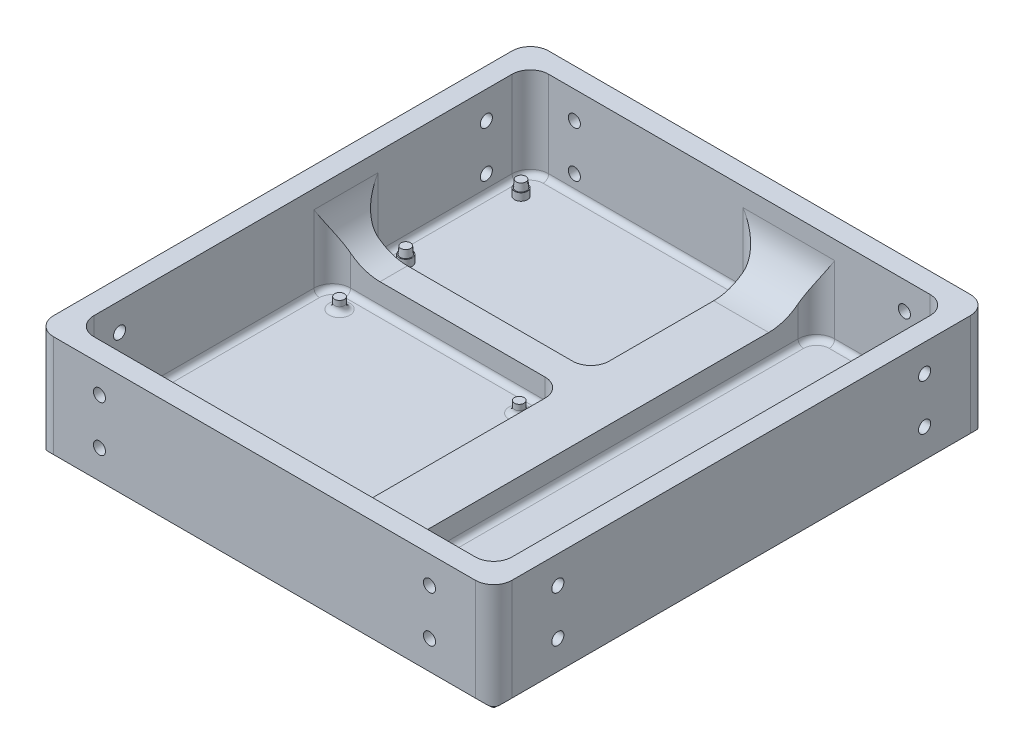
SolidWorks part; units mm, degrees
ref_plane "Front Plane" through (0, 0, 0) normal (0, 0, 1) x (1, 0, 0)
ref_plane "Top Plane" through (0, 0, 0) normal (0, 1, 0) x (1, 0, 0)
ref_plane "Right Plane" through (0, 0, 0) normal (1, 0, 0) x (0, 0, -1)
sketch "Sketch1" plane through (0, 0, 0) normal (0, 1, 0) x (1, 0, 0)
  line L1 (-83.6568, 40.258) -> (46.3432, 40.258)
  line L2 (-83.6568, 40.258) -> (-83.6568, -99.742)
  line L3 (-83.6568, -99.742) -> (46.3432, -99.742)
  line L4 (46.3432, 40.258) -> (46.3432, -99.742)
  dimension "D1" = 140
  dimension "D2" = 130
extrude "Boss-Extrude2" add sketch "Sketch1" along normal blind 10
sketch "Sketch3" plane through (0, 10, 0) normal (0, 1, 0) x (1, 0, 0)
  line L0 (-83.6568, -99.742) -> (46.3432, -99.742) construction
  line L1 (-83.6568, 40.258) -> (-83.6568, -99.742) construction
  circle A0 centre (-68.6568, -26.742) radius 1.3
  circle A1 centre (-19.6568, -26.742) radius 1.3
  circle A2 centre (-68.6568, -84.742) radius 1.3
  circle A3 centre (-19.6568, -84.742) radius 1.3
  dimension "D1" = 49
  dimension "D2" = 58
  dimension "D3" = 49
  dimension "D6" = 2.6
  dimension "D7" = 2.6
  dimension "D8" = 2.6
  dimension "D9" = 2.6
  dimension "D4" = 15
  dimension "D5" = 15
extrude "Boss-Extrude4" add sketch "Sketch3" along normal blind 2
sketch "Sketch4" plane through (0, 12, 0) normal (0, 1, 0) x (1, 0, 0)
  circle A0 centre (-68.6568, -26.742) radius 1.15
  circle A1 centre (-68.6568, -84.742) radius 1.15
  circle A2 centre (-19.6568, -84.742) radius 1.15
  circle A3 centre (-19.6568, -26.742) radius 1.15
  dimension "D1" = 2.3
  dimension "D2" = 2.3
  dimension "D3" = 2.3
  dimension "D4" = 2.3
extrude "Boss-Extrude5" add sketch "Sketch4" along normal blind 3 draft 5 draft outward yes
chamfer "Chamfer1" distance 1.5 angle 45 4 edges at (-19.6568, 15, 86.1545) (-68.6568, 15, 28.1545) (-19.6568, 15, 28.1545) (-68.6568, 15, 86.1545)
sketch "Sketch5" plane through (0, 10, 0) normal (0, 1, 0) x (1, 0, 0)
  line L0 (46.3432, 40.258) -> (-83.6568, 40.258) construction
  line L1 (-83.6568, -99.742) -> (-73.6568, -99.742)
  line L2 (-83.6568, -99.742) -> (-83.6568, 40.258)
  line L3 (-83.6568, 40.258) -> (-73.6568, 40.258)
  line L4 (-73.6568, -89.742) -> (-73.6568, 30.258)
  line L5 (46.3432, -99.742) -> (46.3432, 40.258) construction
  line L6 (46.3432, 40.258) -> (-83.6568, 40.258)
  line L7 (46.3432, 40.258) -> (46.3432, 30.258)
  line L8 (36.3432, 30.258) -> (-73.6568, 30.258)
  line L9 (-83.6568, 40.258) -> (-83.6568, 30.258)
  line L10 (-83.6568, -99.742) -> (46.3432, -99.742)
  line L11 (-83.6568, -99.742) -> (-83.6568, -89.742)
  line L12 (-73.6568, -89.742) -> (36.3432, -89.742)
  line L13 (46.3432, -99.742) -> (46.3432, -89.742)
  line L15 (46.3432, -99.742) -> (36.3432, -99.742)
  line L16 (46.3432, -99.742) -> (46.3432, 40.258)
  line L17 (46.3432, 40.258) -> (36.3432, 40.258)
  line L18 (36.3432, -89.742) -> (36.3432, 30.258)
  line M3 (-83.6568, 40.258) -> (-83.6568, -99.742)
  line M4 (-83.6568, -99.742) -> (46.3432, -99.742)
  line M5 (46.3432, -99.742) -> (46.3432, 40.258)
  line M6 (46.3432, 40.258) -> (-83.6568, 40.258)
  dimension "D1" = 10
  dimension "D2" = 10
  dimension "D3" = 10
  dimension "D4" = 10
extrude "Boss-Extrude6" add sketch "Sketch5" along normal blind 20 contours L6 L2 L10 L18 L12 L4 L8 M6 M3 M4 M5
sketch "Sketch7" plane through (0, 30, 0) normal (0, 1, 0) x (1, 0, 0)
  line L0 (46.3432, 40.258) -> (-83.6568, 40.258) construction
  line L1 (-75.6568, 32.258) -> (38.3432, 32.258)
  line L2 (-75.6568, 32.258) -> (-75.6568, -91.742)
  line L3 (-75.6568, -91.742) -> (38.3432, -91.742)
  line L4 (38.3432, 32.258) -> (38.3432, -91.742)
  line L5 (-83.6568, -99.742) -> (46.3432, -99.742) construction
  line L6 (-83.6568, 40.258) -> (-83.6568, -99.742) construction
  line L7 (46.3432, -99.742) -> (46.3432, 40.258) construction
  line L9 (-73.6568, 30.258) -> (36.3432, 30.258)
  line L10 (-73.6568, 30.258) -> (-73.6568, -89.742)
  line L11 (-73.6568, -89.742) -> (36.3432, -89.742)
  line L12 (36.3432, 30.258) -> (36.3432, -89.742)
  dimension "D1" = 8
  dimension "D2" = 8
  dimension "D3" = 8
  dimension "D4" = 8
extrude "Cut-Extrude2" cut sketch "Sketch7" against normal up to surface (20 mm away) up to face at (-18.6568, 10, 29.742)
sketch "Sketch9" plane through (0, 10, 0) normal (0, 1, 0) x (1, 0, 0)
  line L0 (38.3432, -91.742) -> (-75.6568, -91.742) construction
  line L1 (-12.6568, -91.742) -> (2.3432, -91.742)
  line L2 (-12.6568, -91.742) -> (-12.6568, 32.258)
  line L3 (-12.6568, 32.258) -> (2.3432, 32.258)
  line L4 (2.3432, -91.742) -> (2.3432, 32.258)
  line L5 (38.3432, -91.742) -> (38.3432, 32.258) construction
  line L6 (-75.6568, 32.258) -> (38.3432, 32.258) construction
  dimension "D1" = 15
  dimension "D2" = 36
  dimension "D3" = 0
extrude "Boss-Extrude8" add sketch "Sketch9" along normal blind 5
sketch "Sketch10" plane through (0, 10, 0) normal (0, 1, 0) x (1, 0, 0)
  line L0 (-75.6568, -91.742) -> (-75.6568, 32.258) construction
  line L1 (-75.6568, -21.742) -> (-12.6568, -21.742)
  line L2 (-75.6568, -21.742) -> (-75.6568, -14.242)
  line L3 (-75.6568, -14.242) -> (-12.6568, -14.242)
  line L4 (-12.6568, -21.742) -> (-12.6568, -14.242)
  line L5 (-12.6568, 32.258) -> (-12.6568, -91.742) construction
  circle A0 centre (-68.6568, -26.742) radius 1.2817 construction
  dimension "D1" = 7.5
  dimension "D2" = 5
extrude "Boss-Extrude9" add sketch "Sketch10" along normal blind 5
sketch "Sketch12" plane through (0, 10, 0) normal (0, 1, 0) x (1, 0, 0)
  line L1 (-75.6568, 32.258) -> (-12.6568, 32.258)
  line L2 (-75.6568, 32.258) -> (-75.6568, -14.242)
  line L3 (-75.6568, -14.242) -> (-12.6568, -14.242)
  line L4 (-12.6568, 32.258) -> (-12.6568, -14.242)
  line L5 (2.3432, 32.258) -> (38.3432, 32.258)
  line L6 (2.3432, 32.258) -> (2.3432, -91.742)
  line L7 (2.3432, -91.742) -> (38.3432, -91.742)
  line L8 (38.3432, 32.258) -> (38.3432, -91.742)
  line L9 (-12.6568, -91.742) -> (-75.6568, -91.742)
  line L10 (-12.6568, -91.742) -> (-12.6568, -21.742)
  line L11 (-12.6568, -21.742) -> (-75.6568, -21.742)
  line L12 (-75.6568, -91.742) -> (-75.6568, -21.742)
  circle A0 centre (-68.6846, -26.742) radius 1.3279
  circle A1 centre (-68.6568, -26.742) radius 0.0279 construction
  circle A2 centre (-19.6568, -26.7699) radius 1.3279
  circle A3 centre (-19.6568, -26.742) radius 0.0279 construction
  circle A4 centre (-19.6289, -84.742) radius 1.2539
  circle A5 centre (-19.6568, -84.742) radius 0.0279 construction
  circle A6 centre (-68.6568, -84.7141) radius 1.2539
  circle A7 centre (-68.6568, -84.742) radius 0.0279 construction
extrude "Cut-Extrude6" cut sketch "Sketch12" against normal blind 5
sketch "Sketch14" plane through (0, 15, 0) normal (0, 1, 0) x (1, 0, 0)
  line L1 (-75.6568, -21.742) -> (-15.6932, -21.742)
  line L2 (-75.6568, -21.742) -> (-75.6568, -90.2178)
  line L3 (-75.6568, -90.2178) -> (-15.6932, -90.2178)
  line L4 (-15.6932, -21.742) -> (-15.6932, -90.2178)
extrude "Cut-Extrude9" cut sketch "Sketch14" against normal blind 7
sketch "Sketch16" plane through (0, 15, 0) normal (0, 1, 0) x (1, 0, 0)
  line L1 (-75.6568, 32.258) -> (38.3432, 32.258)
  line L2 (-75.6568, 32.258) -> (-75.6568, -91.742)
  line L3 (-75.6568, -91.742) -> (38.3432, -91.742)
  line L4 (38.3432, 32.258) -> (38.3432, -91.742)
extrude "Cut-Extrude10" cut sketch "Sketch16" against normal blind 3
fillet "Fillet12" radius 13 3 edges at (-5.1568, 12, 91.742) (-5.1568, 12, -32.258) (-75.6568, 12, 17.992)
fillet "Fillet13" radius 5 12 edges at (2.3432, 15, 91.742) (-75.6568, 15, 21.742) (-12.6568, 8.5, 21.742) (-75.6568, 17.5, 91.742) (38.3432, 17.5, -32.258) (-12.6568, 15, 91.742) (38.3432, 17.5, 91.742) (2.3432, 15, -32.258) (-75.6568, 15, 14.242) (-12.6568, 8.5, 14.242) (-12.6568, 15, -32.258) (-75.6568, 17.5, -32.258)
fillet "Fillet14" radius 5 4 edges at (46.3432, 15, 99.742) (46.3432, 15, -40.258) (-83.6568, 15, -40.258) (-83.6568, 15, 99.742)
fillet "Fillet15" radius 1.5 28 edges at (3.8077, 5, -30.7935) (20.3432, 5, -32.258) (36.8788, 5, -30.7935) (38.3432, 5, 29.742) (36.8788, 5, 90.2775) (20.3432, 5, 91.742) (3.8077, 5, 90.2775) (2.3432, 5, 29.742) (-74.1923, 5, -30.7935) (-44.1568, 5, -32.258) (-14.1212, 5, -30.7935) (-12.6568, 5, -9.008) (-14.1212, 5, 12.7775) (-44.1568, 5, 14.242) (-74.1923, 5, 12.7775) (-75.6568, 5, -9.008) (-14.1212, 5, 23.2065) (-12.6568, 5, 56.742) (-14.1212, 5, 90.2775) (-44.1568, 5, 91.742) (-74.1923, 5, 90.2775) (-75.6568, 5, 56.742) (-74.1923, 5, 23.2065) (-44.1568, 5, 21.742) (-68.6846, 5, 28.0699) (-19.6568, 5, 28.0977) (-19.6289, 5, 85.9958) (-68.6568, 5, 85.968)
sketch "Sketch24" plane through (46.3432, 0, 0) normal (1, 0, 0) x (0, 0, -1)
  line L0 (-94.742, 0) -> (35.258, 0) construction
  line L2 (40.258, 30) -> (40.258, 0) construction
  circle A0 centre (-79.742, 22.5) radius 1.65
  circle A1 centre (-79.742, 10) radius 1.65
  circle A2 centre (20.258, 22.5) radius 1.65
  circle A3 centre (20.258, 10) radius 1.65
  dimension "D1" = 12.5
  dimension "D5" = 20
  dimension "D6" = 12.5
  dimension "D2" = 10
  dimension "D3" = 20
  dimension "D4" = 20
  dimension "D7" = 10
extrude "Cut-Extrude16" cut sketch "Sketch24" against normal blind 10
sketch "Sketch25" plane through (-83.6568, 0, 0) normal (-1, 0, 0) x (0, 0, 1)
  line L0 (-40.258, 0) -> (-40.258, 30) construction
  line L1 (-35.258, 0) -> (94.742, 0) construction
  line L2 (99.742, 30) -> (99.742, 0) construction
  circle A0 centre (-20.258, 22.5) radius 1.65
  circle A1 centre (-20.258, 10) radius 1.65
  circle A2 centre (79.742, 10) radius 1.65
  circle A3 centre (79.742, 22.5) radius 1.65
  dimension "D1" = 20
  dimension "D3" = 10
  dimension "D4" = 20
  dimension "D2" = 22.5
extrude "Cut-Extrude17" cut sketch "Sketch25" against normal blind 10
sketch "Sketch26" plane through (0, 0, 99.742) normal (0, 0, 1) x (1, 0, 0)
  line L0 (-83.6568, 0) -> (-83.6568, 30) construction
  line L1 (-78.6568, 0) -> (41.3432, 0) construction
  line L2 (46.3432, 30) -> (46.3432, 0) construction
  circle A0 centre (-63.6568, 22.5) radius 1.65
  circle A1 centre (-63.6568, 10) radius 1.65
  circle A2 centre (26.3432, 10) radius 1.65
  circle A3 centre (26.3432, 22.5) radius 1.65
  dimension "D1" = 20
  dimension "D3" = 12.5
  dimension "D4" = 20
  dimension "D2" = 22.5
extrude "Cut-Extrude18" cut sketch "Sketch26" against normal blind 10
sketch "Sketch27" plane through (0, 0, -40.258) normal (0, 0, -1) x (-1, 0, 0)
  line L0 (-46.3432, 0) -> (-46.3432, 30) construction
  line L2 (-41.3432, 0) -> (78.6568, 0) construction
  line L3 (83.6568, 30) -> (83.6568, 0) construction
  circle A0 centre (-26.3432, 22.5) radius 1.65
  circle A1 centre (-26.3432, 10) radius 1.65
  circle A2 centre (63.6568, 22.5) radius 1.65
  circle A3 centre (63.6568, 10) radius 1.65
  point P10 (83.6568, 15)
  dimension "D1" = 20
  dimension "D3" = 12.5
  dimension "D4" = 20
  dimension "D2" = 22.5
extrude "Cut-Extrude19" cut sketch "Sketch27" against normal blind 10
fillet "Fillet17" radius 5 8 edges at (44.8788, 0, -38.7935) (-18.6568, 0, -40.258) (-82.1923, 0, -38.7935) (-83.6568, 0, 29.742) (-82.1923, 0, 98.2775) (-18.6568, 0, 99.742) (44.8788, 0, 98.2775) (46.3432, 0, 29.742)
sketch "Sketch30" plane through (0, 5, 0) normal (0, 1, 0) x (1, 0, 0)
  line L0 (-75.6568, -9.242) -> (-75.6568, 27.258) construction
  line L1 (-17.6568, -14.242) -> (-70.6568, -14.242) construction
  circle A0 centre (-70.6568, 24.723) radius 1.75
  circle A1 centre (-70.6568, -6.707) radius 1.75
  dimension "D1" = 5
  dimension "D2" = 3.5
  dimension "3.5" = 3.5
  dimension "D3" = 31.43
  dimension "D4" = 7.535
extrude "Boss-Extrude10" add sketch "Sketch30" along normal blind 2
sketch "Sketch31" plane through (0, 7, 0) normal (0, 1, 0) x (1, 0, 0)
  circle A0 centre (-70.6568, 24.723) radius 1.5
  circle A1 centre (-70.6568, -6.707) radius 1.5
extrude "Boss-Extrude11" add sketch "Sketch31" along normal blind 2 draft 5
sketch "Sketch32" plane through (0, 30, 0) normal (0, 1, 0) x (1, 0, 0)
  line L1 (-83.6568, 35.258) -> (-83.6568, -94.742) construction
  line L2 (-83.6568, 40.258) -> (46.3432, 40.258)
  line L3 (-83.6568, 40.258) -> (-83.6568, -99.742)
  line L4 (-83.6568, -99.742) -> (46.3432, -99.742)
  line L6 (46.3432, 40.258) -> (46.3432, -99.742)
  line L7 (-81.1568, 37.758) -> (43.8432, 37.758)
  line L8 (-81.1568, 37.758) -> (-81.1568, -97.242)
  line L9 (-81.1568, -97.242) -> (43.8432, -97.242)
  line L10 (43.8432, 37.758) -> (43.8432, -97.242)
  dimension "D1" = 130
  dimension "D2" = 2.5
  dimension "D3" = 2.5
  dimension "D4" = 2.5
  dimension "D5" = 2.5
  dimension "D6" = 0
extrude "Cut-Extrude22" cut sketch "Sketch32" against normal blind 50
fillet "Fillet18" radius 5 4 edges at (-81.1568, 16.614, 97.242) (43.8432, 16.614, -37.758) (-81.1568, 16.614, -37.758) (43.8432, 16.614, 97.242)
